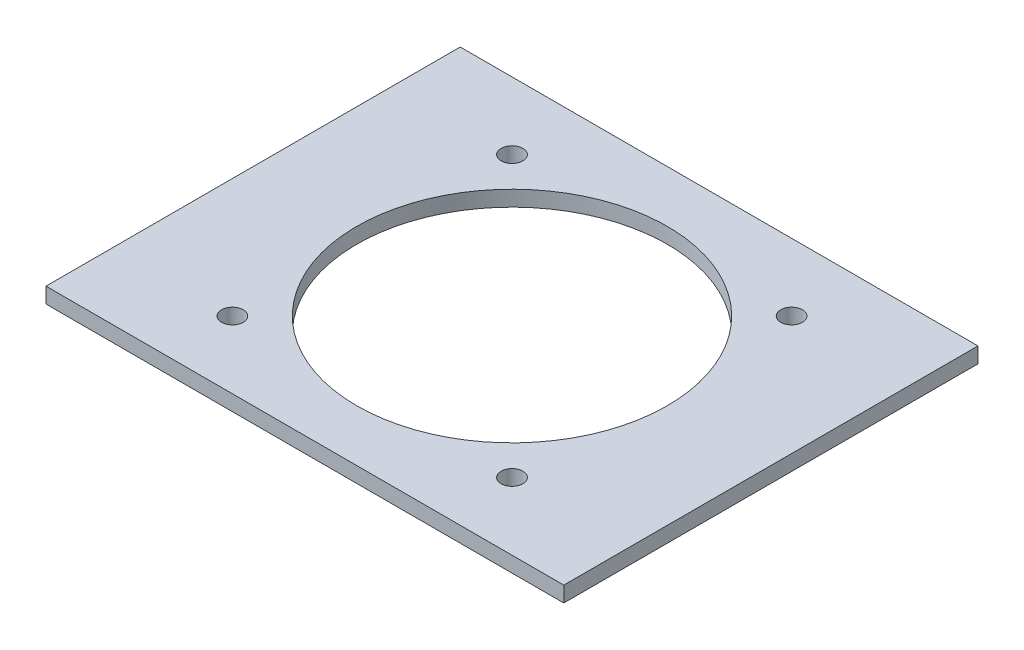
SolidWorks part; units mm, degrees
material "6061-T6 (SS)"
ref_plane "前视基准面" through (0, 0, 0) normal (0, 0, 1) x (1, 0, 0)
ref_plane "上视基准面" through (0, 0, 0) normal (0, 1, 0) x (1, 0, 0)
ref_plane "右视基准面" through (0, 0, 0) normal (1, 0, 0) x (0, 0, -1)
sketch "草图1" plane through (0, 0, 0) normal (0, 1, 0) x (1, 0, 0)
  line L1 (-50, 40) -> (50, 40)
  line L2 (-50, 40) -> (-50, -40)
  line L3 (-50, -40) -> (50, -40)
  line L4 (50, 40) -> (50, -40)
  line L5 (-50, 40) -> (50, -40) construction
  line L6 (-50, -40) -> (50, 40) construction
  circle A0 centre (0, 0) radius 30
  point P0 (0, 0)
  dimension "D3" = 60
  dimension "D1" = 80
  dimension "D2" = 100
extrude "凸台-拉伸1" add sketch "草图1" along normal blind 3
sketch "草图2" plane through (0, 3, 0) normal (0, 1, 0) x (1, 0, 0)
  circle A0 centre (27, 27) radius 2.1
  dimension "D1" = 4.2
extrude "切除-拉伸1" cut sketch "草图2" against normal blind 10
pattern_circular "阵列(圆周)1" count 4 over 360 about axis through (0, 3, 0) along (0, -1, 0) of "切除-拉伸1" reverse direction yes
